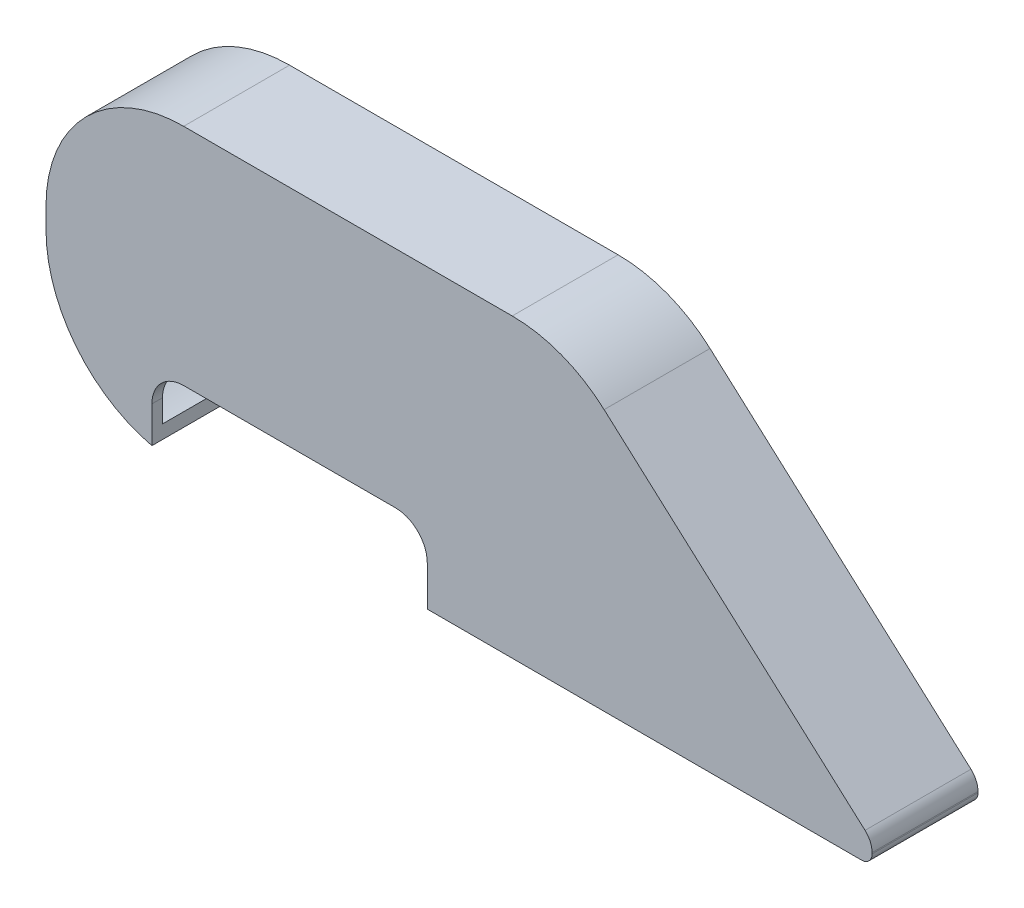
SolidWorks part; units mm, degrees
ref_plane "Front Plane" through (0, 0, 0) normal (0, 0, 1) x (1, 0, 0)
ref_plane "Top Plane" through (0, 0, 0) normal (0, 1, 0) x (1, 0, 0)
ref_plane "Right Plane" through (0, 0, 0) normal (1, 0, 0) x (0, 0, -1)
sketch "Sketch1" plane through (0, 0, 0) normal (0, 0, 1) x (1, 0, 0)
  line L1 (0, 0) -> (80, 0)
  line L2 (0, 0) -> (0, 30)
  line L3 (0, 30) -> (80, 30)
  line L4 (80, 0) -> (80, 30)
  dimension "D1" = 30
  dimension "D2" = 80
extrude "Boss-Extrude1" add sketch "Sketch1" along normal blind 10
sketch "Sketch2" plane through (0, 0, 10) normal (0, 0, 1) x (1, 0, 0)
  line L0 (80, 0) -> (80, 3)
  line L1 (80, 0) -> (80, 30) construction
  line L3 (0, 30) -> (50, 30)
  line L4 (80, 30) -> (0, 30) construction
  line L5 (80, 3) -> (50, 30)
  dimension "D1" = 3
  dimension "D2" = 50
extrude "Cut-Extrude2" cut sketch "Sketch2" against normal blind 10 and the other way through all contours L0 L5 L3
sketch "Sketch9" plane through (0, 0, 10) normal (0, 0, 1) x (1, 0, 0)
  line L0 (1.0044, 1.037) -> (79.0059, 0.9937)
  line L1 (79.0059, 0.9937) -> (79.0059, 3)
  line L2 (79.0059, 3) -> (50, 29.0013)
  line L3 (50, 29.0013) -> (1.0044, 28.9984)
  line L4 (1.0044, 28.9984) -> (1.0044, 1.037)
extrude "Cut-Extrude3" cut sketch "Sketch9" against normal blind 10 flip side to cut
sketch "Sketch14" plane through (0, 0, 0) normal (0, 0, -1) x (-1, 0, 0)
  line L0 (-50, 28.0032) -> (-2.0127, 28.0032)
  line L1 (-2.0127, 28.0032) -> (-2.0081, 2.0355)
  line L2 (-2.0081, 2.0355) -> (-78.0027, 1.9919)
  line L3 (-78.0027, 1.9919) -> (-78.0027, 3)
  line L4 (-78.0027, 3) -> (-50, 28.0032)
extrude "Cut-Extrude5" cut sketch "Sketch14" against normal blind 9
fillet "Fillet13" radius 13 1 edges at (2.0127, 28.0032, 4.5)
fillet "Fillet14" radius 13 1 edges at (2.0081, 2.0355, 4.5)
fillet "Fillet15" radius 13 1 edges at (50, 28.0032, 4.5)
fillet "Fillet17" radius 13 1 edges at (1.0044, 28.9984, 5)
fillet "Fillet18" radius 13 1 edges at (1.0044, 1.037, 5)
fillet "Fillet19" radius 13 1 edges at (50, 29.0013, 5)
fillet "Fillet20" radius 2 1 edges at (79.0059, 3, 5)
fillet "Fillet21" radius 1 1 edges at (79.0059, 0.9937, 5)
fillet "Fillet22" radius 0.5 1 edges at (78.0027, 1.9919, 4.5)
fillet "Fillet23" radius 1 1 edges at (78.0027, 3, 4.5)
sketch "Sketch15" plane through (0, 0, 10) normal (0, 0, 1) x (1, 0, 0)
  line L1 (11.0044, 7.8004) -> (37.0044, 7.8004)
  line L2 (11.0044, 7.8004) -> (11.0044, 0.8004)
  line L3 (11.0044, 0.8004) -> (37.0044, 0.8004)
  line L4 (37.0044, 7.8004) -> (37.0044, 0.8004)
  point P4 (37.0044, 4.3004)
  dimension "D1" = 26
  dimension "D2" = 7
  dimension "D3" = 10
extrude "Cut-Extrude6" cut sketch "Sketch15" against normal blind 15
fillet "Fillet24" radius 3 1 edges at (11.0044, 7.8004, 9.5)
fillet "Fillet25" radius 3 1 edges at (37.0044, 7.8004, 9.5)
